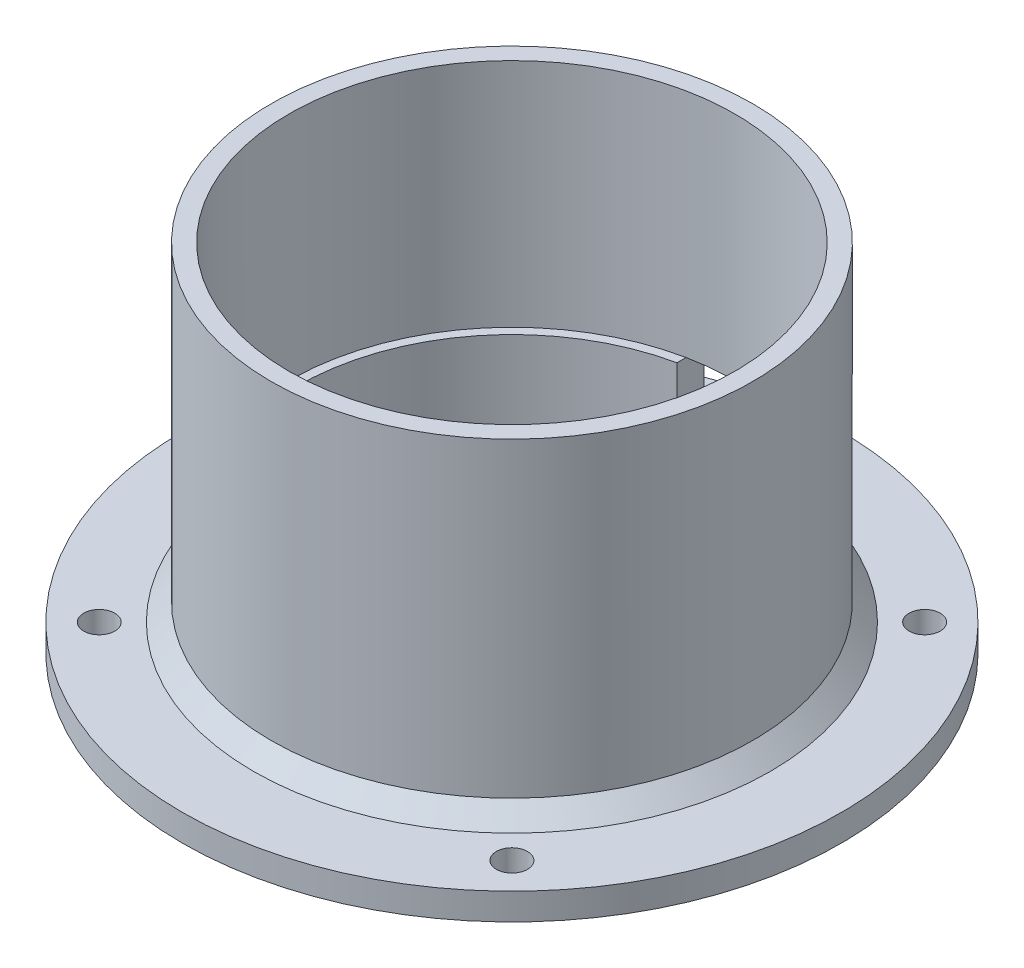
SolidWorks part; units mm, degrees
material "ABS"
ref_plane "Front Plane" through (0, 0, 0) normal (0, 0, 1) x (1, 0, 0)
ref_plane "Top Plane" through (0, 0, 0) normal (0, 1, 0) x (1, 0, 0)
ref_plane "Right Plane" through (0, 0, 0) normal (1, 0, 0) x (0, 0, -1)
sketch "Sketch2" plane through (0, 0, 0) normal (0, 0, 1) x (1, 0, 0)
  line L0 (0, 0) -> (0, -8.9596) construction
  line L1 (25.1, 13) -> (27.1, 13)
  line L2 (27.1, 13) -> (27.1, -24)
  line L3 (27.1, -24) -> (37.1, -24)
  line L4 (37.1, -24) -> (37.1, -27)
  line L5 (37.1, -27) -> (24.1, -27)
  line L6 (25.1, -13) -> (25.1, 13)
  line L8 (24.1, -27) -> (24.1, -13)
  line L9 (24.1, -13) -> (25.1, -13)
  point P5 (25.1, 0)
  dimension "D1" = 2
  dimension "D2" = 3
  dimension "D3" = 40
  dimension "D4" = 50.2
  dimension "D5" = 10
  dimension "D6" = 14
  dimension "D7" = 3
revolve "Revolve1" add sketch "Sketch2" angle 360 about L0
sketch "Sketch3" plane through (0, -24, 0) normal (0, 1, 0) x (1, 0, 0)
  line L0 (-23.2285, 23.2285) -> (23.2285, -23.2285) construction
  line L1 (-26.2337, -26.2337) -> (26.2337, 26.2337) construction
  line L2 (0, 0) -> (-53.7099, 0) construction
  circle A0 centre (0, 0) radius 37.1 construction
  circle A1 centre (0, 0) radius 32.85 construction
  circle A6 centre (-23.2285, 23.2285) radius 1.75
  circle A7 centre (23.2285, 23.2285) radius 1.75
  circle A8 centre (23.2285, -23.2285) radius 1.75
  circle A9 centre (-23.2285, -23.2285) radius 1.75
  dimension "D1" = 65.7
  dimension "D2" = 3.5
  dimension "D3" = 45
extrude "Cut-Extrude1" cut sketch "Sketch3" against normal blind 10
sketch "Sketch5" plane through (0, 0, 0) normal (0, 0, 1) x (1, 0, 0)
  line L0 (0, 13) -> (0, -27) construction
  line L1 (27.1, 13) -> (-27.1, 13) construction
  line L2 (-37.1, -27) -> (37.1, -27) construction
  line L3 (37.1, -24) -> (-37.1, -24) construction
  line L4 (-5, -23) -> (5, -23)
  line L5 (-5, -23) -> (-5, -13)
  line L6 (-5, -13) -> (5, -13)
  line L7 (5, -23) -> (5, -13)
  point P10 (0, -13)
  dimension "D1" = 10
  dimension "D2" = 10
  dimension "D3" = 1
extrude "Cut-Extrude3" cut sketch "Sketch5" against normal blind 50
chamfer "Chamfer1" distance 2 angle 45 1 edges at (0, -24, 27.1)
